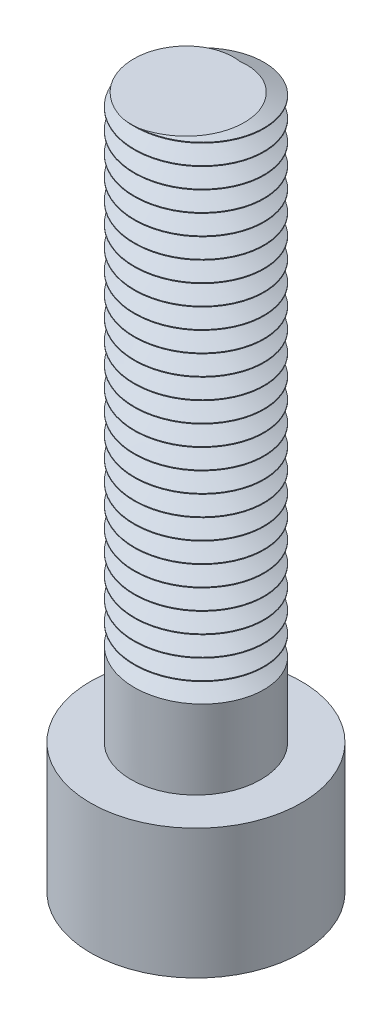
SolidWorks part; units mm, degrees
ref_plane "Front Plane" through (0, 0, 0) normal (0, 0, 1) x (1, 0, 0)
ref_plane "Top Plane" through (0, 0, 0) normal (0, 1, 0) x (1, 0, 0)
ref_plane "Right Plane" through (0, 0, 0) normal (1, 0, 0) x (0, 0, -1)
sketch "Sketch1" plane through (0, 0, 0) normal (0, 1, 0) x (1, 0, 0)
  circle A0 centre (0, 0) radius 6.5
extrude "Boss-Extrude1" add sketch "Sketch1" along normal blind 8
sketch "Sketch2" plane through (0, 8, 0) normal (0, 1, 0) x (1, 0, 0)
  circle A0 centre (0, 0) radius 4
extrude "Boss-Extrude2" add sketch "Sketch2" along normal blind 35
sketch "Sketch3" plane through (0, 43, 0) normal (0, 1, 0) x (1, 0, 0)
  circle A0 centre (0, 0) radius 4
curve "Helix/Spiral1" pitch 1.25 height 30 radius 4 left hand yes centre (0, 43, 0) axis (0, -1, 0) start towards (0, 0, -1)
ref_plane "Plane1" through (0, 13, -4) normal (-0.9988, -0.0497, 0) x (0, 0, 1)
sketch "Sketch4" plane through (0, 13, -4) normal (-0.9988, -0.0497, 0) x (0, 0, 1)
  line L0 (-0.0031, 0.5982) -> (-0.0031, -0.6018)
  line L1 (-0.0031, -0.6018) -> (1.2969, -0.0018)
  line L2 (1.2969, -0.0018) -> (-0.0031, 0.5982)
  point P2 (-0.0031, 1.2482)
  point P4 (-0.0031, -0.0018)
  dimension "D1" = 0.6
  dimension "D2" = 0.6
  dimension "D3" = 0
  dimension "D4" = 1.3
sweep "Cut-Sweep2" cut profiles "Sketch4" path "Helix/Spiral1" align with end faces yes
sketch "Sketch5" plane through (0, 0, 0) normal (0, -1, 0) x (1, 0, 0)
  line L0 (-3.4641, 0) -> (-1.7321, 3)
  line L1 (-1.7321, 3) -> (1.7321, 3)
  line L2 (1.7321, 3) -> (3.4641, 0)
  line L3 (3.4641, 0) -> (1.7321, -3)
  line L4 (1.7321, -3) -> (-1.7321, -3)
  line L5 (-1.7321, -3) -> (-3.4641, 0)
  dimension "D1" = 6
  dimension "D2" = 6
  dimension "D3" = 6
  dimension "D4" = 3
  dimension "D5" = 3
  dimension "D6" = 3
extrude "Cut-Extrude1" cut sketch "Sketch5" against normal blind 5.5
fillet "Fillet1" radius 1 6 edges at (-2.5981, 0, 1.5) (-2.5981, 0, -1.5) (0, 0, -3) (2.5981, 0, -1.5) (2.5981, 0, 1.5) (0, 0, 3)
